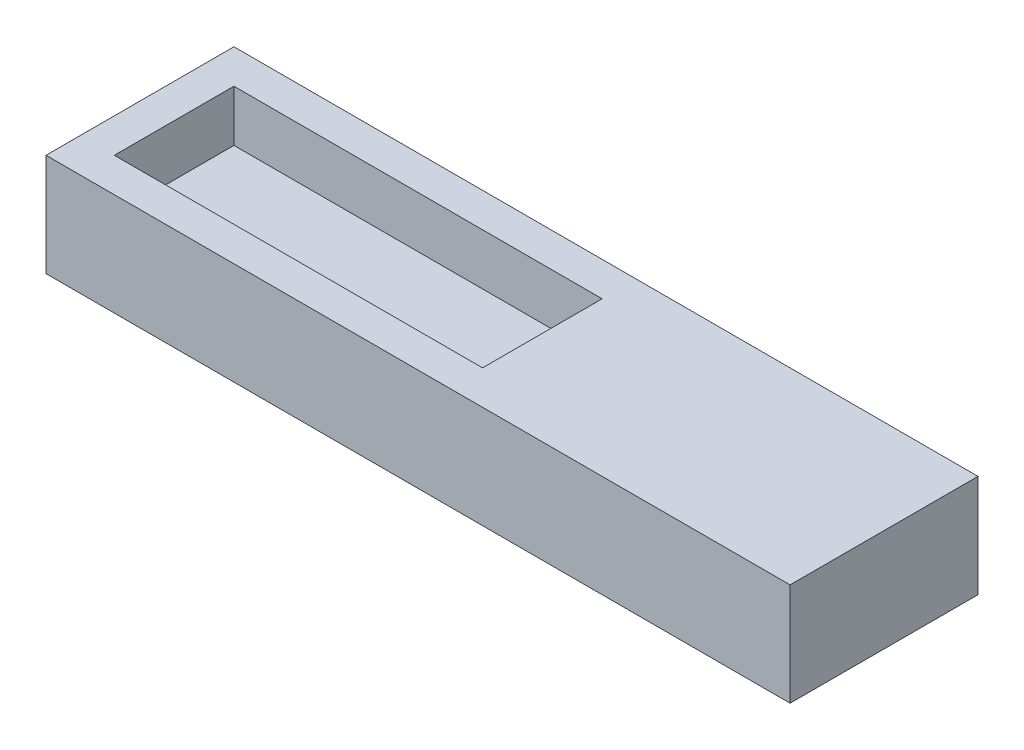
SolidWorks part; units mm, degrees
ref_plane "Front Plane" through (0, 0, 0) normal (0, 0, 1) x (1, 0, 0)
ref_plane "Top Plane" through (0, 0, 0) normal (0, 1, 0) x (1, 0, 0)
ref_plane "Right Plane" through (0, 0, 0) normal (1, 0, 0) x (0, 0, -1)
sketch "Sketch1" plane through (0, 0, 0) normal (0, 1, 0) x (1, 0, 0)
  line L1 (0, 0) -> (43.55, 0)
  line L2 (0, 0) -> (0, -11)
  line L3 (0, -11) -> (43.55, -11)
  line L4 (43.55, 0) -> (43.55, -11)
  line L5 (2, -2) -> (23.55, -2)
  line L6 (2, -2) -> (2, -9)
  line L7 (2, -9) -> (23.55, -9)
  line L8 (23.55, -2) -> (23.55, -9)
  point P10 (2, -5.5)
  point P11 (0, -5.5)
  dimension "D1" = 21.55
  dimension "D2" = 7
  dimension "D3" = 2
  dimension "D4" = 2
  dimension "D5" = 20
extrude "Boss-Extrude1" add sketch "Sketch1" along normal blind 3
extrude "Boss-Extrude2" add sketch "Sketch1<2>" against normal blind 3 contours L8 L5 L6 L7 | L4 L1 L2 L3 L5 L8 L7 L6 region at (25.9117, 0, 5.5) region at (12.775, 0, 5.5)
sketch "Sketch1<2>" plane through (0, 0, 0) normal (0, 1, 0) x (1, 0, 0) same geometry as "Sketch1"
sketch "Sketch2" plane through (0, 0, 0) normal (0, 1, 0) x (1, 0, 0)
  line L0 (2, -9) -> (9, -2) construction
  line L4 (23.55, -2) -> (2, -2)
  line L5 (2, -2) -> (2, -9)
  line L6 (2, -9) -> (23.55, -9)
  line L7 (23.55, -9) -> (23.55, -2)
  line L8 (23.55, -2) -> (2, -2)
  line L9 (2, -2) -> (2, -9)
  line L10 (2, -9) -> (23.55, -9)
  line L11 (23.55, -9) -> (23.55, -2)
  point P2 (5.5, -5.5)
  dimension "D2" = 45
  dimension "D1" = 0
ref_axis "servoAxis" through (5.5, 0, 5.5) along (0, 1, 0)
ref_plane "Plane1" through (0, 0, 5.5) normal (0, 0, -1) x (-1, 0, 0)
ref_axis "cameraAxis" through (45.7275, 0, 5.5) along (-1, 0, 0)
